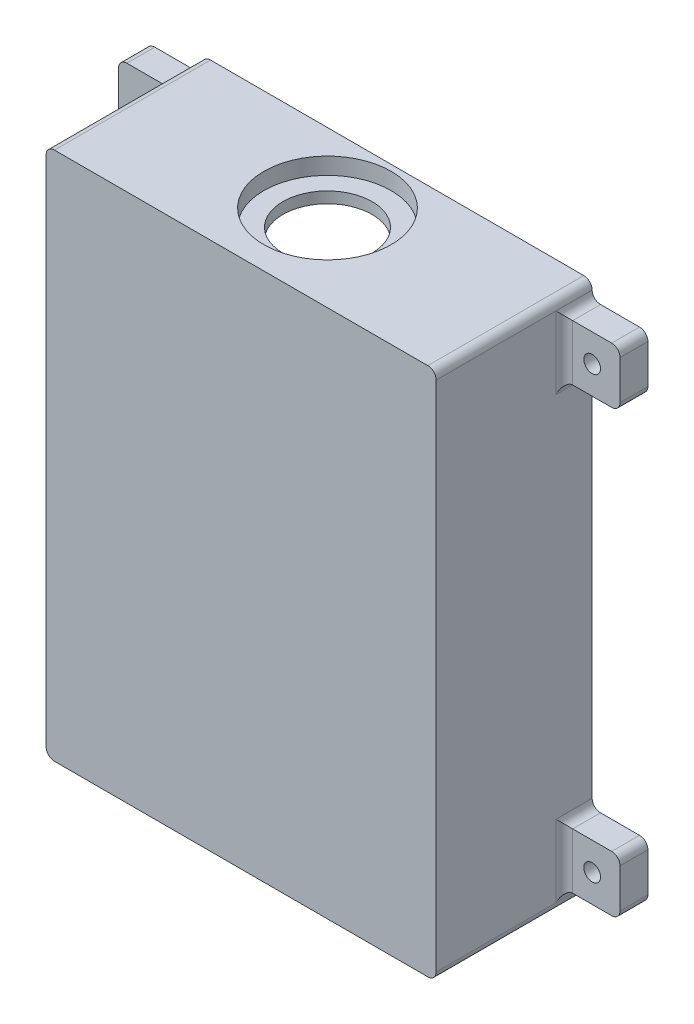
SolidWorks part; units mm, degrees
note: The reader was unsure of these and kept them because the rebuilt part matched: shared geometry of "Sketch1<7>", "Sketch1<6>", "Sketch1<9>", "Sketch3<3>".
ref_plane "Front Plane" through (0, 0, 0) normal (0, 0, 1) x (1, 0, 0)
ref_plane "Top Plane" through (0, 0, 0) normal (0, 1, 0) x (1, 0, 0)
ref_plane "Right Plane" through (0, 0, 0) normal (1, 0, 0) x (0, 0, -1)
sketch "Sketch1" plane through (0, 0, 0) normal (0, 0, 1) x (1, 0, 0)
  line L0 (0, 47.5) -> (0, -47.5) construction
  line L1 (-35, -47.5) -> (35, -47.5)
  line L2 (-35, -47.5) -> (-35, 47.5)
  line L3 (-35, 47.5) -> (35, 47.5)
  line L4 (35, -47.5) -> (35, 47.5)
  line L5 (-35, -47.5) -> (35, 47.5) construction
  line L6 (-35, 47.5) -> (35, -47.5) construction
  line L7 (-40, -34.5) -> (-40, -44.5) construction
  line L8 (35, 44.5) -> (45, 44.5)
  line L9 (35, 44.5) -> (35, 34.5)
  line L10 (35, 34.5) -> (45, 34.5)
  line L11 (45, 44.5) -> (45, 34.5)
  line L12 (-35, -44.5) -> (-45, -44.5)
  line L13 (-35, -44.5) -> (-35, -34.5)
  line L14 (-35, -34.5) -> (-45, -34.5)
  line L15 (-45, -44.5) -> (-45, -34.5)
  line L16 (-45, -39.5) -> (-35, -39.5) construction
  line L17 (40, 44.5) -> (40, 34.5) construction
  line L18 (45, 39.5) -> (35, 39.5) construction
  line L19 (-30, 42.5) -> (30, 42.5)
  line L20 (30, -42.5) -> (30, 42.5)
  line L21 (-30, -42.5) -> (30, -42.5)
  line L22 (-30, -42.5) -> (-30, 42.5)
  line L23 (-35, 0) -> (35, 0) construction
  line L25 (55, 0) -> (-55, 0) construction
  line L26 (35, -44.5) -> (45, -44.5)
  line L27 (45, -44.5) -> (45, -34.5)
  line L28 (35, -34.5) -> (45, -34.5)
  line L29 (-35, 34.5) -> (-45, 34.5)
  line L30 (-45, 44.5) -> (-45, 34.5)
  line L31 (-35, 44.5) -> (-45, 44.5)
  circle A0 centre (0.7077, 27.586) radius 1.85
  circle A1 centre (0.7077, -25.5) radius 1.85
  circle A2 centre (40, 39.5) radius 1.5
  circle A3 centre (-40, -39.5) radius 1.5
  circle A4 centre (-32.5, 45) radius 2.5 construction
  circle A5 centre (32.5, 45) radius 2.5 construction
  circle A6 centre (32.5, -45) radius 2.5 construction
  circle A7 centre (-32.5, -45) radius 2.5 construction
  circle A8 centre (-32.5, -45) radius 1.5 construction
  circle A9 centre (32.5, -45) radius 1.5 construction
  circle A10 centre (-32.5, 45) radius 1.5 construction
  circle A11 centre (32.5, 45) radius 1.5 construction
  circle A12 centre (0.7077, 27.586) radius 2.85
  circle A13 centre (0.7077, -25.5) radius 2.85
  circle A14 centre (40, -39.5) radius 1.5
  circle A15 centre (-40, 39.5) radius 1.5
  point P0 (0, 0)
  dimension "D3" = 53.086
  dimension "D4" = 22
  dimension "D5" = 3.7
  dimension "D7" = 3
  dimension "D11" = 1
  dimension "D12" = 5
  dimension "D1" = 70
  dimension "D2" = 95
  dimension "D6" = 10
  dimension "D8" = 3
  dimension "D9" = 3
  dimension "D14" = 34.2923
  dimension "D10" = 5
  dimension "D13" = 1
extrude "Base" add sketch "Sketch1" along normal blind 28 contours A4 L3 L2 | A10 L19 A4 L22 | L19 A5 L3 A4 | L2 A7 L22 A4 | A10 L22 A4 L19 | L21 A8 L22 A7 | L1 A7 L2 | L22 A8 L21 A7 | L21 A7 L1 A6 | A9 L21 A6 L20 | A6 L1 L4 | A6 L4 A5 L20 | A9 L20 A6 L21 | L22 A7 L21 A6 L20 A5 L19 A4 A1 A0 | A0 | A1 | L3 A5 L4 | L19 A11 L20 A5 | L20 A11 L19 A5 | L19 A10 L22 | A11 L19 L20 | L21 A9 L20 | L20 A9 L21 | A11 L20 L19 | L22 A10 L19 | A8 L22 L21 | A8 L21 L22 | A12 A0 | A13 A1 | L28 L27 L26
extrude "Mounting Holes" add sketch "Sketch1<7>" along normal blind 5 contours L11 L8 L4 L10 A2 | L28 L4 L26 L27 A14 | L15 L12 L2 L14 A3 | L2 L31 L30 L29 A15
sketch "Sketch1<7>" plane through (0, 0, 0) normal (0, 0, 1) x (1, 0, 0) same geometry as "Sketch1"
extrude "Cavity" cut sketch "Sketch1<6>" along normal offset from surface (25 mm away) 3 contours L22 L21 L20 L19 A13 A12 | A12 A0 | A0 | A1 | A13 A1 up to face at (0, 0, 28)
sketch "Sketch1<6>" plane through (0, 0, 0) normal (0, 0, 1) x (1, 0, 0) same geometry as "Sketch1"
extrude "Standoff" add sketch "Sketch1<9>" against normal blind 3 from surface at 25 contours A12 A0 | A13 A1 starting at face at (0, 0, 25)
sketch "Sketch1<9>" plane through (0, 0, 0) normal (0, 0, 1) x (1, 0, 0) same geometry as "Sketch1"
sketch "Sketch3" plane through (7.7077, 47.5, 0) normal (0, -1, 0) x (0, 0, 1)
  line L3 (25, 7.7077) -> (0, 7.7077) construction
  line L8 (25, 9.85) -> (25, 4.15) construction
  circle A0 centre (12.5, 7.7077) radius 8
  circle A1 centre (12.5, 7.7077) radius 11.415
  point P11 (12.5, 7.7077)
  dimension "D1" = 16
  dimension "D3" = 22.8299
extrude "PG9" cut sketch "Sketch3" along normal up to surface (5 mm away) contours L3 A0 | A0 L3 up to face at (0, 42.5, 12.5)
extrude "Cut-Extrude4" cut sketch "Sketch3<3>" along normal offset from surface (3 mm away) 2 up to face at (0, 42.5, 20.5)
sketch "Sketch3<3>" plane through (7.7077, 47.5, 0) normal (0, -1, 0) x (0, 0, 1) same geometry as "Sketch3"
fillet "External Fillet" radius 1.5 24 edges at (35, 47.5, 14) (35, -47.5, 14) (-35, -47.5, 14) (-35, 47.5, 14) (45, -44.5, 2.5) (45, -34.5, 2.5) (35, -34.5, 2.5) (35, -44.5, 2.5) (35, 34.5, 2.5) (45, 44.5, 2.5) (35, 44.5, 2.5) (45, 34.5, 2.5) (-35, 44.5, 2.5) (-45, 44.5, 2.5) (-45, 34.5, 2.5) (-35, 34.5, 2.5) (-35, -34.5, 2.5) (-45, -34.5, 2.5) (-45, -44.5, 2.5) (-35, -44.5, 2.5) (35, -39.5, 5) (35, 39.5, 5) (-35, 39.5, 5) (-35, -39.5, 5)
